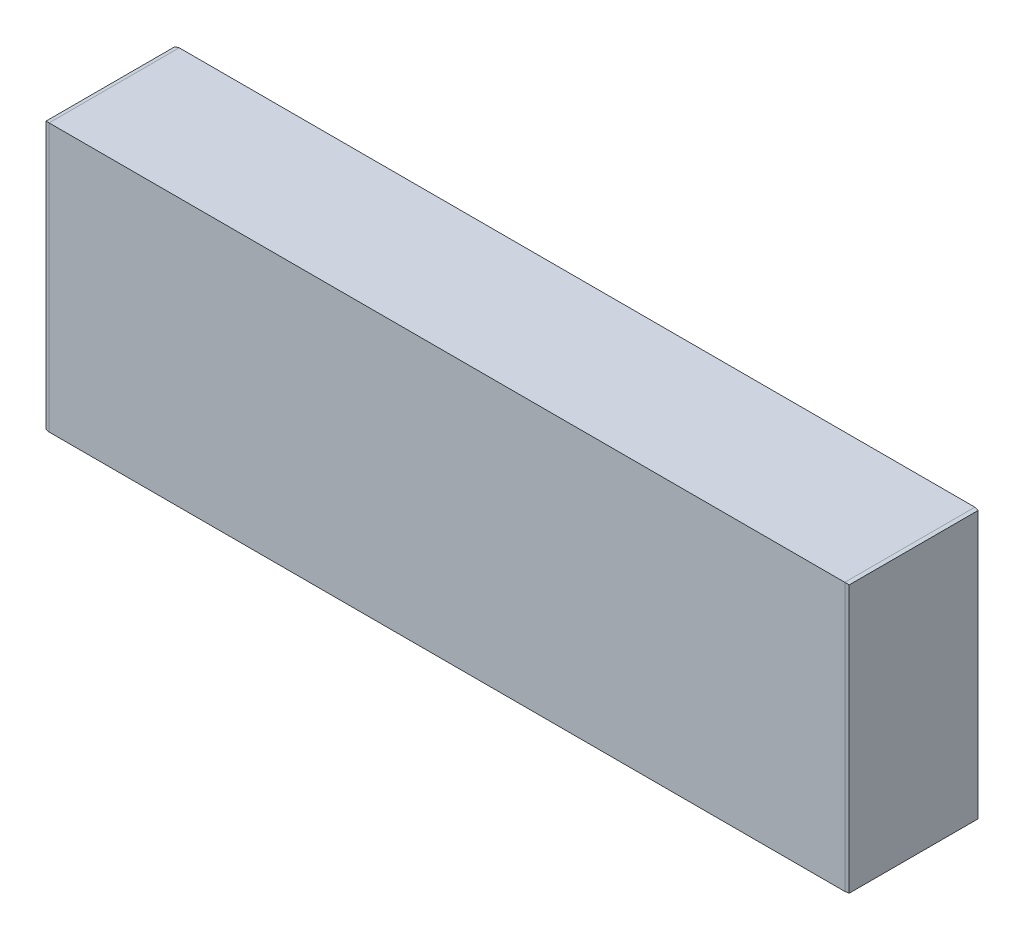
SolidWorks part; units mm, degrees
ref_plane "Front Plane" through (0, 0, 0) normal (0, 0, 1) x (1, 0, 0)
ref_plane "Top Plane" through (0, 0, 0) normal (0, 1, 0) x (1, 0, 0)
ref_plane "Right Plane" through (0, 0, 0) normal (1, 0, 0) x (0, 0, -1)
sketch "Sketch1" plane through (0, 0, 0) normal (0, 0, 1) x (1, 0, 0)
  line L1 (-45.3301, 26.9451) -> (167.6699, 26.9451)
  line L2 (-45.3301, 26.9451) -> (-45.3301, -44.0549)
  line L3 (-45.3301, -44.0549) -> (167.6699, -44.0549)
  line L4 (167.6699, 26.9451) -> (167.6699, -44.0549)
  dimension "D1" = 213
  dimension "D2" = 71
extrude "Boss-Extrude1" add sketch "Sketch1" along normal blind 34.5
chamfer "Chamfer1" distance 1 angle 10 3 edges at (-45.3301, -8.5549, 34.5) (-45.3301, -8.5549, 0) (-45.3301, 26.9451, 17.25) first distance on face at (61.1699, -8.5549, 34.5) first distance on face at (61.1699, -8.5549, 0) first distance on face at (61.1699, 26.9451, 17.25)
chamfer "Chamfer2" distance 1 angle 10 3 edges at (167.6699, -8.5549, 0) (167.6699, -8.5549, 34.5) (167.6699, 26.9451, 17.25) first distance on face at (61.6699, -8.5549, 0) first distance on face at (61.6699, -8.5549, 34.5) first distance on face at (61.6699, 26.9451, 17.25)
sketch "Sketch3" plane through (-45.3301, 0, 0) normal (-1, 0, 0) x (0, 0, 1)
  line L0 (18.2561, -14.9433) -> (18.2561, -35.97) construction
  line L1 (5.1763, -17.6597) -> (29.3237, -17.6597)
  line L2 (5.1763, -17.6597) -> (5.1763, -33.8573)
  line L3 (5.1763, -33.8573) -> (29.3237, -33.8573)
  line L4 (29.3237, -17.6597) -> (29.3237, -33.8573)
  line L5 (6.8058, -19.1688) -> (10.8058, -19.1688)
  line L6 (6.8058, -19.1688) -> (6.8058, -32.5494)
  line L7 (6.8058, -32.5494) -> (10.8058, -32.5494)
  line L8 (10.8058, -19.1688) -> (10.8058, -32.5494)
  line L9 (12.4353, -19.1688) -> (16.4353, -19.1688)
  line L10 (12.4353, -19.1688) -> (12.4353, -32.5494)
  line L11 (12.4353, -32.5494) -> (16.4353, -32.5494)
  line L12 (16.4353, -19.1688) -> (16.4353, -32.5494)
  line L13 (18.0647, -19.1688) -> (22.0647, -19.1688)
  line L14 (18.0647, -19.1688) -> (18.0647, -32.5494)
  line L15 (18.0647, -32.5494) -> (22.0647, -32.5494)
  line L16 (22.0647, -19.1688) -> (22.0647, -32.5494)
  line L17 (23.6942, -19.1688) -> (27.6942, -19.1688)
  line L18 (23.6942, -19.1688) -> (23.6942, -32.5494)
  line L19 (23.6942, -32.5494) -> (27.6942, -32.5494)
  line L20 (27.6942, -19.1688) -> (27.6942, -32.5494)
  line L21 (5.1763, -19.1688) -> (6.8058, -19.1688) construction
  line L22 (10.8058, -19.1688) -> (12.4353, -19.1688) construction
  line L23 (16.4353, -19.1688) -> (18.0647, -19.1688) construction
  line L24 (22.0647, -19.1688) -> (23.6942, -19.1688) construction
  line L25 (27.6942, -19.1688) -> (29.3237, -19.1688) construction
  line L26 (34.3237, -44.0549) -> (34.3237, 26.7688) construction
  line L27 (0.1763, 26.7688) -> (0.1763, -44.0549) construction
  line L28 (34.3237, -44.0549) -> (0.1763, -44.0549) construction
  line L29 (10.8058, -32.5494) -> (10.8058, -33.8573) construction
  line L30 (16.4353, -32.5494) -> (16.4353, -33.8573) construction
  line L31 (22.0647, -32.5494) -> (22.0647, -33.8573) construction
  line L32 (27.6942, -32.5494) -> (27.6942, -33.8573) construction
  dimension "D1" = 4
  dimension "D2" = 4
  dimension "D3" = 4
  dimension "D4" = 4
  dimension "D5" = 5
  dimension "D6" = 5
  dimension "D7" = 10.1976
extrude "Cut-Extrude2" cut sketch "Sketch3" against normal blind 1
sketch "Sketch4" plane through (-45.3301, 0, 0) normal (-1, 0, 0) x (0, 0, 1)
  line L0 (8.6763, -39.3573) -> (8.6763, -41.974) construction
  line L1 (8.1763, -35.8573) -> (9.1763, -35.8573)
  line L2 (8.1763, -35.8573) -> (8.1763, -38.3573)
  line L3 (8.1763, -41.8573) -> (9.1763, -41.8573)
  line L4 (9.1763, -35.8573) -> (9.1763, -38.3573)
  line L5 (5.6763, -38.3573) -> (8.1763, -38.3573)
  line L6 (5.6763, -38.3573) -> (5.6763, -39.3573)
  line L7 (5.6763, -39.3573) -> (8.1763, -39.3573)
  line L8 (11.6763, -38.3573) -> (11.6763, -39.3573)
  line L9 (8.954, -38.8573) -> (13.6707, -38.8573) construction
  line L10 (5.1763, -33.8573) -> (29.3237, -33.8573) construction
  line L11 (0.1763, 26.7688) -> (0.1763, -44.0549) construction
  line L12 (13.6707, -38.8573) -> (32.3354, -38.8573) construction
  line L13 (22.7204, -38.3573) -> (28.7204, -38.3573)
  line L14 (22.7204, -38.3573) -> (22.7204, -39.3573)
  line L15 (22.7204, -39.3573) -> (28.7204, -39.3573)
  line L16 (28.7204, -38.3573) -> (28.7204, -39.3573)
  line L17 (9.1763, -38.3573) -> (11.6763, -38.3573)
  line L18 (8.1763, -39.3573) -> (8.1763, -41.8573)
  line L19 (9.1763, -39.3573) -> (11.6763, -39.3573)
  line L20 (9.1763, -39.3573) -> (9.1763, -41.8573)
  dimension "D1" = 1
  dimension "D2" = 1
  dimension "D3" = 6
  dimension "D5" = 6
  dimension "D6" = 3
  dimension "D7" = 2
  dimension "D8" = 5.5
  dimension "D9" = 6
  dimension "D10" = 1
  dimension "D11" = 0.5
extrude "Cut-Extrude3" cut sketch "Sketch4" against normal blind 1
